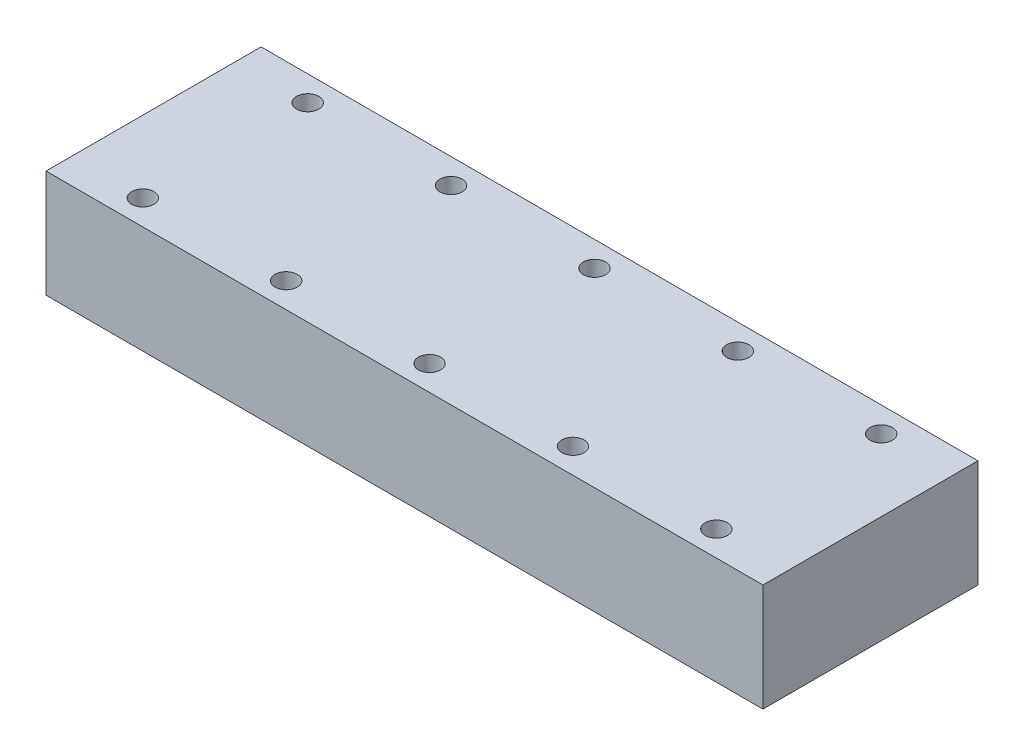
SolidWorks part; units mm, degrees
ref_plane "Front Plane" through (0, 0, 0) normal (0, 0, 1) x (1, 0, 0)
ref_plane "Top Plane" through (0, 0, 0) normal (0, 1, 0) x (1, 0, 0)
ref_plane "Right Plane" through (0, 0, 0) normal (1, 0, 0) x (0, 0, -1)
sketch "Sketch1" plane through (0, 0, 0) normal (0, 1, 0) x (1, 0, 0)
  line L0 (-55, 0) -> (-55, 30)
  line L1 (-55, 30) -> (45, 30)
  line L2 (45, 30) -> (45, 0)
  line L3 (45, 0) -> (-55, 0)
  dimension "D1" = 100
  dimension "D2" = 30
  dimension "D3" = 0
  dimension "D4" = 55
extrude "Boss-Extrude1" add sketch "Sketch1" along normal blind 15
sketch "Sketch4" plane through (0, 0, 0) normal (0, 1, 0) x (1, 0, 0)
  line L0 (-35, 6) -> (-50, 6)
  line L1 (-50, 6) -> (-50, 24)
  line L2 (-50, 24) -> (-20, 24)
  line L3 (-20, 24) -> (-20, 6)
  line L4 (-20, 6) -> (-35, 6)
  line L5 (-55, 30) -> (-55, 0) construction
  line L9 (45, 30) -> (-55, 30) construction
  line L10 (-55, 0) -> (45, 0) construction
  dimension "D1" = 18
  dimension "D2" = 6
  dimension "D3" = 5
  dimension "D4" = 30
  dimension "D5" = 6
extrude "Cut-Extrude1" cut sketch "Sketch4" against normal blind 8 and the other way blind 10.11
sketch "Sketch3" plane through (0, 0, 0) normal (0, 1, 0) x (1, 0, 0)
  line L0 (45, 15) -> (-55, 15) construction
  line L1 (45, 0) -> (45, 30) construction
  line L2 (-55, 30) -> (-55, 0) construction
  line L3 (40, 15) -> (40, 8.41)
  line L4 (40, 8.41) -> (-40, 6.89)
  line L5 (-40, 6.89) -> (-40, 15)
  line L6 (-40, 15) -> (40, 15)
  line L7 (-20, 6) -> (-20, 24) construction
  dimension "D1" = 6.59
  dimension "D2" = 8.11
  dimension "D3" = 80
  dimension "D4" = 20
revolve "Cut-Revolve1" cut sketch "Sketch3" angle 360 about L0
sketch "Sketch5" plane through (0, 0, 0) normal (0, 1, 0) x (1, 0, 0)
  line L0 (30, 8.22) -> (30, 10.72)
  line L1 (-20, 7.27) -> (40, 8.41) construction
  line L2 (30, 10.72) -> (17.5, 10.4825)
  line L3 (17.5, 10.4825) -> (17.5, 7.9825)
  line L4 (17.5, 7.9825) -> (30, 8.22)
  line L5 (40, 15) -> (-16.9672, 15) construction
  line L6 (40, 8.41) -> (40, 21.59) construction
  dimension "D1" = 2.5
  dimension "D2" = 2.5
  dimension "D3" = 12.5
  dimension "D4" = 10
revolve "Revolve1" add sketch "Sketch5" angle 45 about L5 other way angle 225
sketch "Sketch6" plane through (0, 0, 0) normal (0, 1, 0) x (1, 0, 0)
  line L0 (5, 7.745) -> (5, 10.245)
  line L1 (-20, 7.27) -> (17.5, 7.9825) construction
  line L2 (5, 10.245) -> (-7.5, 10.0075)
  line L3 (-7.5, 10.0075) -> (-7.5, 7.5075)
  line L4 (-7.5, 7.5075) -> (5, 7.745)
  line L5 (40, 15) -> (-17.599, 15) construction
  line L6 (40, 8.41) -> (40, 21.59) construction
  dimension "D1" = 2.5
  dimension "D2" = 2.5
  dimension "D3" = 12.5
  dimension "D4" = 12.5
revolve "Revolve2" add sketch "Sketch6" angle 45 about L5 other way angle 225
sketch "Sketch7" plane through (0, 0, 0) normal (0, 1, 0) x (1, 0, 0)
  line L0 (45, 0) -> (45, 30)
  line L1 (45, 30) -> (-55, 30)
  line L2 (-55, 30) -> (-55, 0)
  line L3 (-55, 0) -> (45, 0)
extrude "Cut-Extrude2" cut sketch "Sketch7" against normal blind 15
fillet "Fillet1" radius 1.2 20 edges at (17.5, 2.6855, -21.4833) (17.5, 1.7288, -19.1736) (5, 1.8197, -19.393) (5, 1.8197, -10.607) (17.5, 2.6855, -8.5167) (17.5, 1.7288, -10.8264) (5, 2.7764, -8.2973) (5, 2.7764, -21.7027) (30, 2.5946, -8.7361) (30, 2.5946, -21.2639) (23.75, 3.1104, -11.8896) (30, 1.6379, -11.0458) (30, 1.6379, -18.9542) (-7.5, 1.9105, -19.6125) (-7.5, 2.8673, -21.9222) (-7.5, 2.8673, -8.0778) (-7.5, 1.9105, -10.3875) (-1.25, 3.4463, -11.5537) (23.75, 3.1104, -18.1104) (-1.25, 3.4463, -18.4463)
ref_plane "Plane1" through (-55, 0, 0) normal (-1, 0, 0) x (0, 0, 1)
sketch "Sketch9" plane through (0, 0, 0) normal (0, 1, 0) x (1, 0, 0)
  line L0 (45, 0) -> (45, 30) construction
  line L3 (45, 30) -> (-55, 30) construction
  line L4 (45, 15) -> (-55.4355, 15) construction
  line L5 (-55, 0) -> (45, 0) construction
  circle A0 centre (35, 26.5) radius 1.55
  circle A1 centre (15, 26.5) radius 1.55
  circle A2 centre (-5, 26.5) radius 1.55
  circle A3 centre (-25, 26.5) radius 1.55
  circle A4 centre (-45, 26.5) radius 1.55
  circle A5 centre (35, 3.5) radius 1.55
  circle A6 centre (15, 3.5) radius 1.55
  circle A7 centre (-5, 3.5) radius 1.55
  circle A8 centre (-25, 3.5) radius 1.55
  circle A9 centre (-45, 3.5) radius 1.55
  dimension "D6" = 3.1
  dimension "D7" = 3.1
  dimension "D8" = 3.1
  dimension "D9" = 3.1
  dimension "D10" = 3.1
  dimension "D21" = 3.1
  dimension "D22" = 3.1
  dimension "D23" = 3.1
  dimension "D24" = 3.1
  dimension "D25" = 3.1
  dimension "D1" = 10
  dimension "D2" = 20
  dimension "D3" = 20
  dimension "D4" = 20
  dimension "D5" = 20
  dimension "D11" = 3.5
  dimension "D12" = 3.5
  dimension "D13" = 3.5
  dimension "D14" = 3.5
  dimension "D15" = 3.5
  dimension "D16" = 3.5
  dimension "D17" = 3.5
  dimension "D18" = 3.5
  dimension "D19" = 3.5
  dimension "D20" = 3.5
fillet "Fillet9" radius 1.2 7 edges at (-35, 10.11, -6) (-50, 5.055, -6) (-50, 5.055, -24) (-50, 10.11, -15) (-35, 10.11, -24) (-20, 7.73, -15) (-20, 10.11, -15)
fillet "Fillet10" radius 0.5 4 edges at (-20.3515, 9.7585, -6.3515) (-20.3515, 9.7585, -23.6485) (-20, 4.455, -6) (-20, 4.455, -24)
extrude "Cut-Extrude3" cut sketch "Sketch9" against normal blind 15 and the other way blind 20
